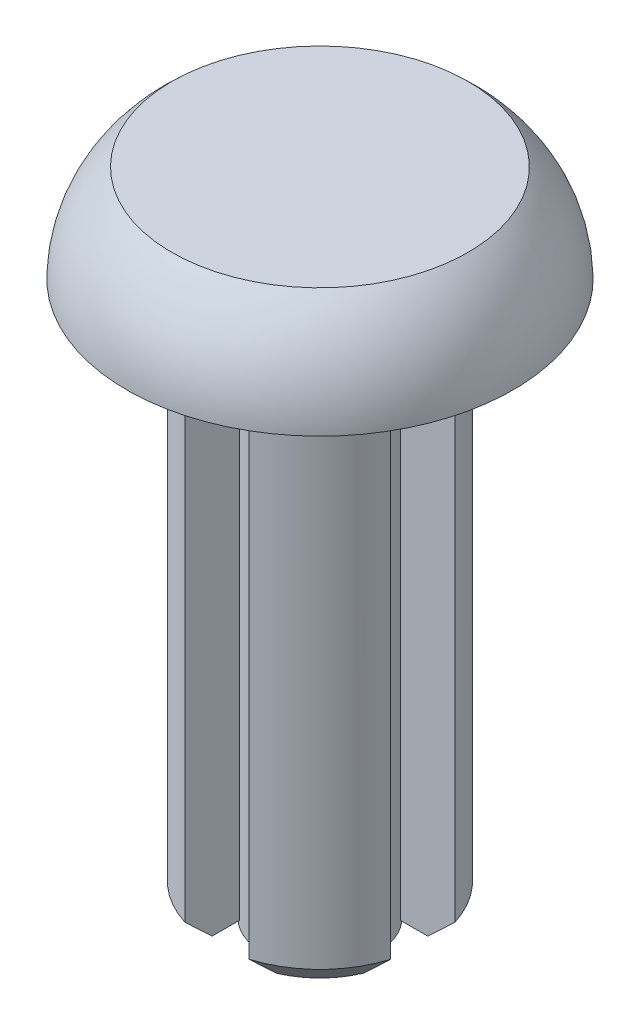
SolidWorks part; units mm, degrees
ref_plane "Front" through (0, 0, 0) normal (0, 0, 1) x (1, 0, 0)
ref_plane "Top" through (0, 0, 0) normal (0, 1, 0) x (1, 0, 0)
ref_plane "Right" through (0, 0, 0) normal (1, 0, 0) x (0, 0, -1)
sketch "Sketch1" plane through (0, 0, 0) normal (0, 0, 1) x (1, 0, 0)
  line L0 (-2.1272, 0.905) -> (-2.1272, -11.4394)
  line L1 (0, 1.905) -> (-2.921, 1.905)
  line L2 (-2.1272, 0.905) -> (-2.4907, 0.905)
  line L3 (-3.81, 0) -> (-2.8103, -0.0228)
  line L4 (-2.1272, -11.4394) -> (0, -11.4394)
  line L5 (0, 1.905) -> (0, -11.4394) construction
  line L6 (0, 1.905) -> (0, -11.4394)
  arc A0 (-2.4907, 0.905) -> (-2.8103, -0.0228) centre (-1.1967, -0.0596) ccw
  arc A1 (-2.921, 1.905) -> (-3.81, 0) centre (-1.1967, -0.0596) ccw
  point P8 (0, 0)
  dimension "D6" = 1.6139
  dimension "D7" = 2.6139
  dimension "D8" = 0.0596
  dimension "D1" = 13.3444
  dimension "D2" = 4.2545
  dimension "D3" = 5.842
  dimension "D4" = 1.905
  dimension "D5" = 0.3635
  dimension "D9" = 1.9278
  dimension "D10" = 1.306
revolve "Revolve1" add sketch "Sketch1" angle 360 about L5
sketch "Sketch2" plane through (0, 0, 0) normal (1, 0, 0) x (0, 0, -1)
  line L0 (1.143, -10.8044) -> (2.1272, -10.8044)
  line L1 (2.1272, -10.8044) -> (2.1272, -11.4394)
  line L2 (1.143, -10.8044) -> (1.143, -11.4394)
  line L3 (0, -11.4394) -> (0, -10.4037) construction
  line L5 (-2.1272, -11.4394) -> (2.1272, -11.4394) construction
  line L6 (2.1272, -11.4394) -> (1.143, -11.4394)
  dimension "D1" = 4.2545
  dimension "D2" = 1.143
  dimension "D3" = 0.635
revolve "Cut-Revolve1" cut sketch "Sketch2" angle 360 about L3
sketch "Sketch3" plane through (0, -10.8044, 0) normal (0, -1, 0) x (1, 0, 0)
  line L0 (0.635, 0.9504) -> (0.635, 2.0303)
  line L1 (-0.635, 2.0303) -> (-0.635, 0.9504)
  line L2 (0, 0) -> (0, 3.5096) construction
  arc A0 (0.635, 0.9504) -> (-0.635, 0.9504) centre (0, 0) ccw
  arc A1 (0.635, 2.0303) -> (-0.635, 2.0303) centre (0, 0) ccw
  circle A2 centre (0, 0) radius 1.143 construction
  circle A3 centre (0, 0) radius 2.1272 construction
  dimension "D1" = 1.27
extrude "Cut-Extrude1" cut sketch "Sketch3" against normal blind 10.16
pattern_circular "CirPattern1" count 4 over 360 about axis through (0, 1.905, 0) along (0, 1, 0) of "Cut-Extrude1"
chamfer "Chamfer1" distance 0.508 angle 45 5 edges at (-1.5042, -10.8044, -1.5042) (1.5042, -10.8044, -1.5042) (-1.5042, -10.8044, 1.5042) (1.5042, -10.8044, 1.5042) (0, -11.4394, -1.143)
ref_axis "Axis1" through (0, -10.2964, 0) along (0, 1, 0)
